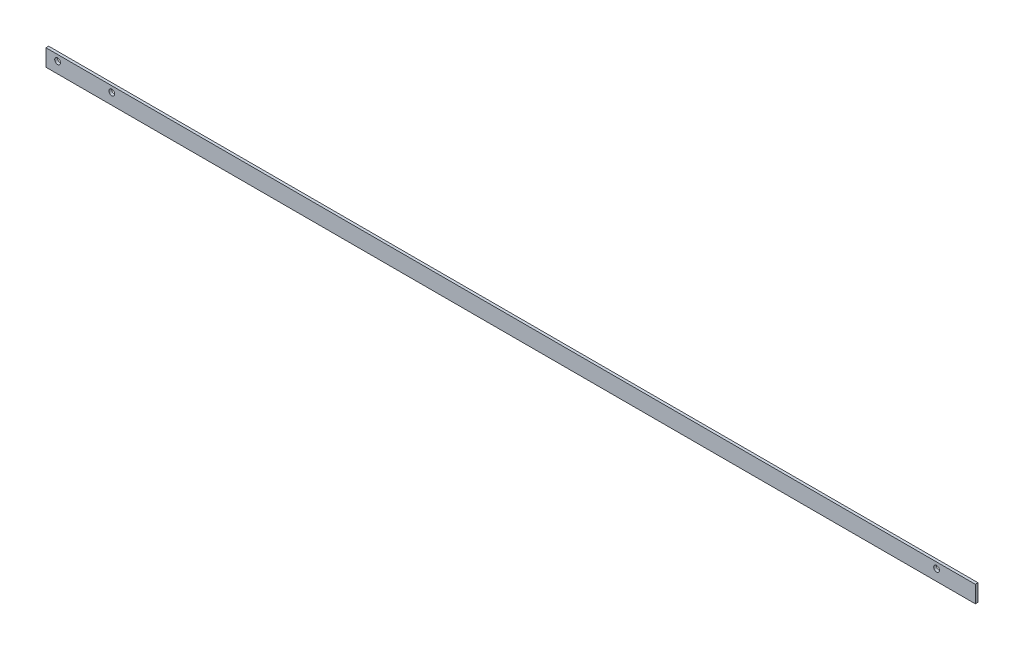
SolidWorks part; units mm, degrees
ref_plane "Front Plane" through (0, 0, 0) normal (0, 0, 1) x (1, 0, 0)
ref_plane "Top Plane" through (0, 0, 0) normal (0, 1, 0) x (1, 0, 0)
ref_plane "Right Plane" through (0, 0, 0) normal (1, 0, 0) x (0, 0, -1)
sketch "Sketch1" plane through (0, 0, 0) normal (0, 0, 1) x (1, 0, 0)
  line L1 (-304.8, -5.5499) -> (304.8, -5.5499)
  line L2 (-304.8, -5.5499) -> (-304.8, 5.5499)
  line L3 (-304.8, 5.5499) -> (304.8, 5.5499)
  line L4 (304.8, -5.5499) -> (304.8, 5.5499)
  line L5 (-304.8, -5.5499) -> (304.8, 5.5499) construction
  line L6 (-304.8, 5.5499) -> (304.8, -5.5499) construction
  point P0 (0, 0)
  dimension "D1" = 609.6
  dimension "D2" = 11.0998
extrude "Boss-Extrude1" add sketch "Sketch1" along normal mid plane 1.778
sketch "Sketch2" plane through (0, 0, 0.889) normal (0, 0, 1) x (1, 0, 0)
  line L0 (304.8, 5.5499) -> (-304.8, 5.5499) construction
  line L1 (-304.8, 5.5499) -> (-304.8, -5.5499) construction
  line L2 (304.8, -5.5499) -> (304.8, 5.5499) construction
  circle A0 centre (-297.18, 1.7399) radius 1.651
  circle A1 centre (-261.62, 1.7399) radius 1.651
  circle A2 centre (279.4, 1.7399) radius 2.6414
  dimension "D2" = 3.302
  dimension "D1" = 3.81
  dimension "D3" = 7.62
  dimension "D4" = 35.56
  dimension "D5" = 25.4
  dimension "D6" = 3.81
hole_wizard "#6 Clearance Hole1" positions "Sketch3" profile "Sketch4" hole size "#6" standard "ANSI Inch" end condition through all
sketch "Sketch3" plane through (0, 0, 0.889) normal (0, 0, 1) x (1, 0, 0)
  point P0 (-297.18, 1.7399)
  point P3 (-261.62, 1.7399)
  point P6 (279.4, 1.7399)
sketch "Sketch4" plane through (-297.18, 1.7399, 0.889) normal (1, 0, 0) x (0, -1, 0)
  line L0 (0, 0) -> (0, 1.778)
  line L1 (0, 1.778) -> (1.8986, 1.778)
  line L2 (1.8986, 1.778) -> (1.8986, 0)
  line L5 (1.8986, 0) -> (0, 0)
  line L11 (0, -6.35) -> (0, 107.95) construction
  dimension "Thru Hole Dia." = 3.7973
  dimension "Thru Hole Depth" = 1.778
